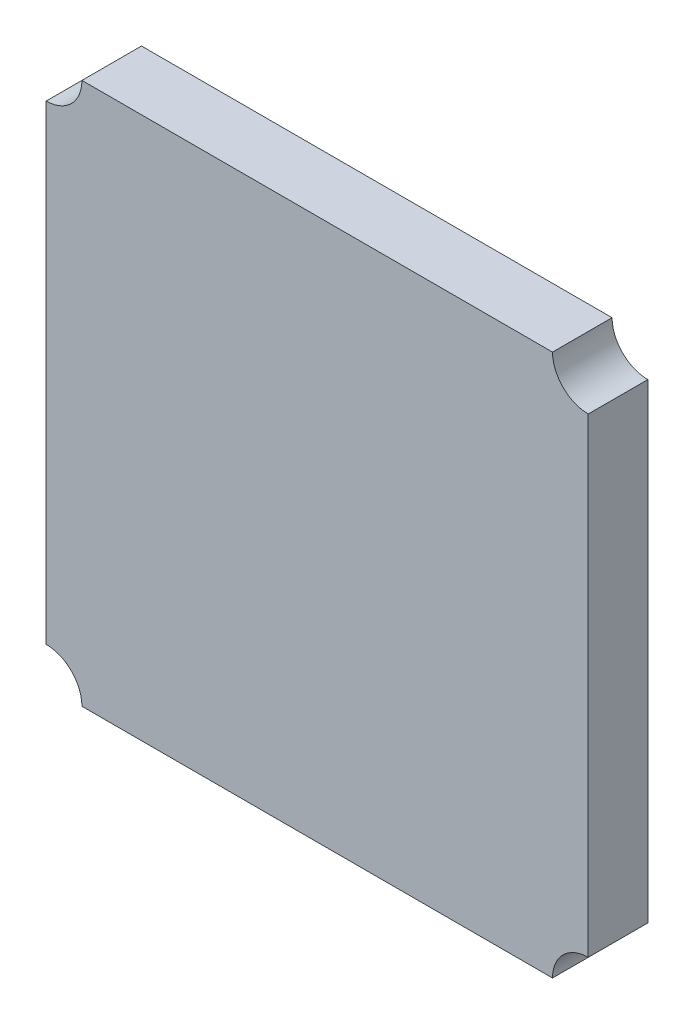
SolidWorks part; units mm, degrees
ref_plane "Plan de face" through (0, 0, 0) normal (0, 0, 1) x (1, 0, 0)
ref_plane "Plan de dessus" through (0, 0, 0) normal (0, 1, 0) x (1, 0, 0)
ref_plane "Plan de droite" through (0, 0, 0) normal (1, 0, 0) x (0, 0, -1)
sketch "Esquisse1" plane through (0, 0, 0) normal (0, 0, 1) x (1, 0, 0)
  line L1 (0, 0) -> (45.5, 0)
  line L2 (0, 0) -> (0, -45.5)
  line L3 (0, -45.5) -> (45.5, -45.5)
  line L4 (45.5, 0) -> (45.5, -45.5)
  arc A1 (3, -45.5) -> (0, -42.5) centre (0, -45.5) ccw
  arc A2 (42.5, -45.5) -> (45.5, -42.5) centre (45.5, -45.5) cw
  arc A3 (45.5, -3) -> (42.5, 0) centre (45.5, 0) cw
  arc A4 (0, -3) -> (3, 0) centre (0, 0) ccw
  dimension "D1" = 45.5
  dimension "D2" = 45.5
  dimension "D3" = 3
  dimension "D4" = 3
  dimension "D5" = 3
  dimension "D6" = 3
extrude "Boss.-Extru.1" add sketch "Esquisse1" along normal blind 5 contours A4 L2 A1 L3 A2 L4 A3 L1 region at (22.75, -22.75, 0)
